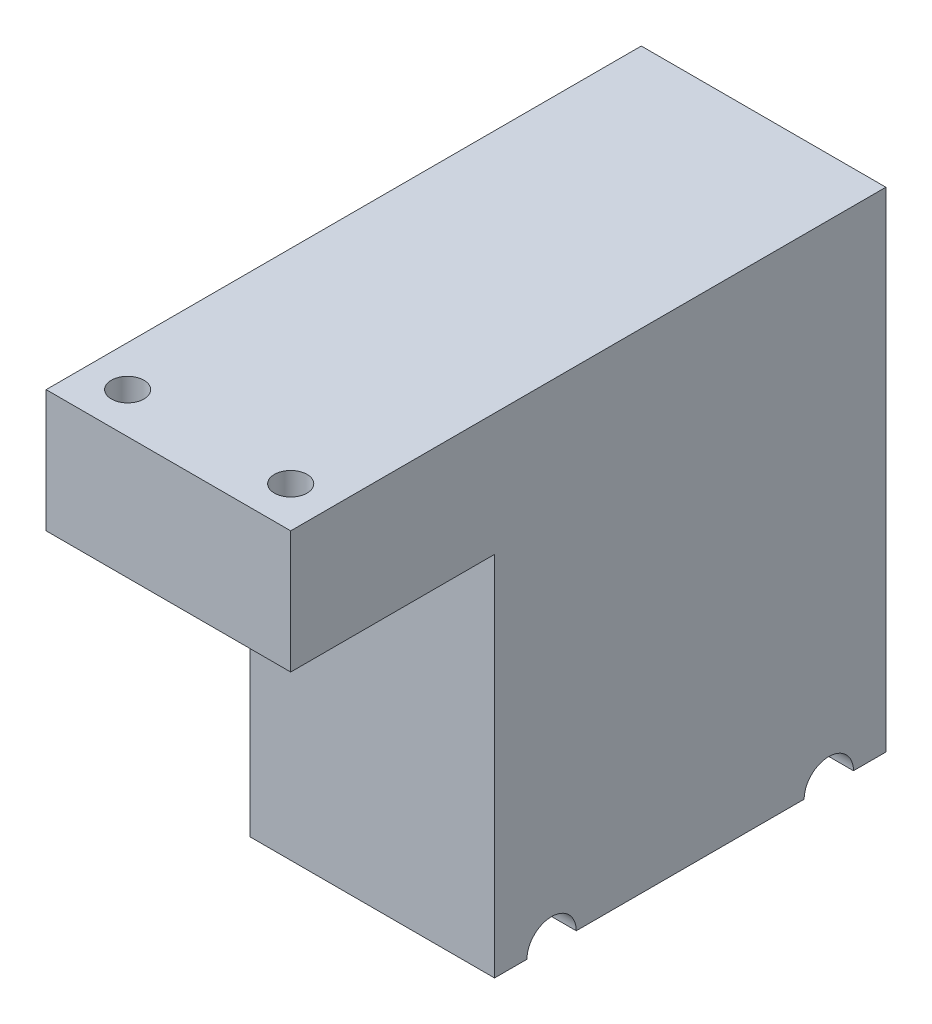
SolidWorks part; units mm, degrees
ref_plane "前视基准面" through (0, 0, 0) normal (0, 0, 1) x (1, 0, 0)
ref_plane "上视基准面" through (0, 0, 0) normal (0, 1, 0) x (1, 0, 0)
ref_plane "右视基准面" through (0, 0, 0) normal (1, 0, 0) x (0, 0, -1)
sketch "草图1" plane through (0, 0, 0) normal (0, 0, 1) x (1, 0, 0)
  line L1 (0, 0) -> (30, 0)
  line L2 (0, 0) -> (0, 95)
  line L3 (0, 95) -> (30, 95)
  line L4 (30, 0) -> (30, 95)
extrude "凸台-拉伸1" add sketch "草图1" along normal blind 48
sketch "草图2" plane through (0, 0, 0) normal (-1, 0, 0) x (0, 0, 1)
  line L1 (48, 95) -> (48, 0) construction
  line L2 (48, 0) -> (0, 0) construction
  circle A0 centre (7, 35) radius 3.005
  circle A1 centre (41, 35) radius 3.005
  circle A2 centre (7, 35) radius 3.025
  circle A3 centre (41, 35) radius 3.025
  dimension "D3" = 6.01
  dimension "D1" = 34
  dimension "D2" = 7
  dimension "D5" = 35
  dimension "D6" = 35
  dimension "D4" = 0.02
extrude "切除-拉伸1" cut sketch "草图2" against normal blind 46 body kept at (0, 0, 0)
sketch "草图3" plane through (0, 0, 48) normal (0, 0, 1) x (1, 0, 0)
  line L0 (30, 0) -> (30, 95) construction
  line L1 (0, 95) -> (30, 95)
  line L2 (0, 95) -> (0, 80)
  line L3 (0, 80) -> (30, 80)
  line L4 (30, 95) -> (30, 80)
extrude "凸台-拉伸2" add sketch "草图3" along normal blind 25
sketch "草图4" plane through (0, 95, 0) normal (0, 1, 0) x (1, 0, 0)
  line L0 (30, -73) -> (30, 0) construction
  line L1 (0, -73) -> (0, 0) construction
  line L2 (30, -73) -> (0, -73) construction
  circle A0 centre (5, -68) radius 2
  circle A2 centre (25, -68) radius 2
  point P6 (0, 0)
  dimension "D1" = 4
  dimension "D4" = 5
  dimension "D2" = 5
  dimension "D3" = 20
  dimension "D5" = 5
extrude "切除-拉伸2" cut sketch "草图4" against normal blind 5
sketch "草图5" plane through (0, 0, 0) normal (-1, 0, 0) x (0, 0, 1)
  line L0 (0, 95) -> (0, 0) construction
  line L1 (0, 35) -> (48, 35)
  line L2 (0, 35) -> (0, 0)
  line L3 (0, 0) -> (48, 0)
  line L4 (48, 35) -> (48, 0)
extrude "切除-拉伸3" cut sketch "草图5" against normal through all
sketch "草图6" plane through (0, 35, 0) normal (0, -1, 0) x (1, 0, 0)
  line L0 (0, 37.975) -> (0, 10.025) construction
  line L1 (0, 37.975) -> (30, 37.975) construction
  line L3 (30, 10.025) -> (0, 10.025) construction
  circle A0 centre (6, 31.975) radius 2
  circle A3 centre (24, 31.975) radius 2
  circle A4 centre (6, 16.025) radius 2
  circle A7 centre (24, 16.025) radius 2
  point P2 (0, 0)
  point P3 (0, 0)
  point P4 (0, 0)
  point P5 (0, 0)
  point P10 (0, 0)
  dimension "D1" = 4
  dimension "D3" = 18
  dimension "D7" = 6
  dimension "D6" = 6
  dimension "D2" = 6
extrude "切除-拉伸4" cut sketch "草图6" against normal blind 5
